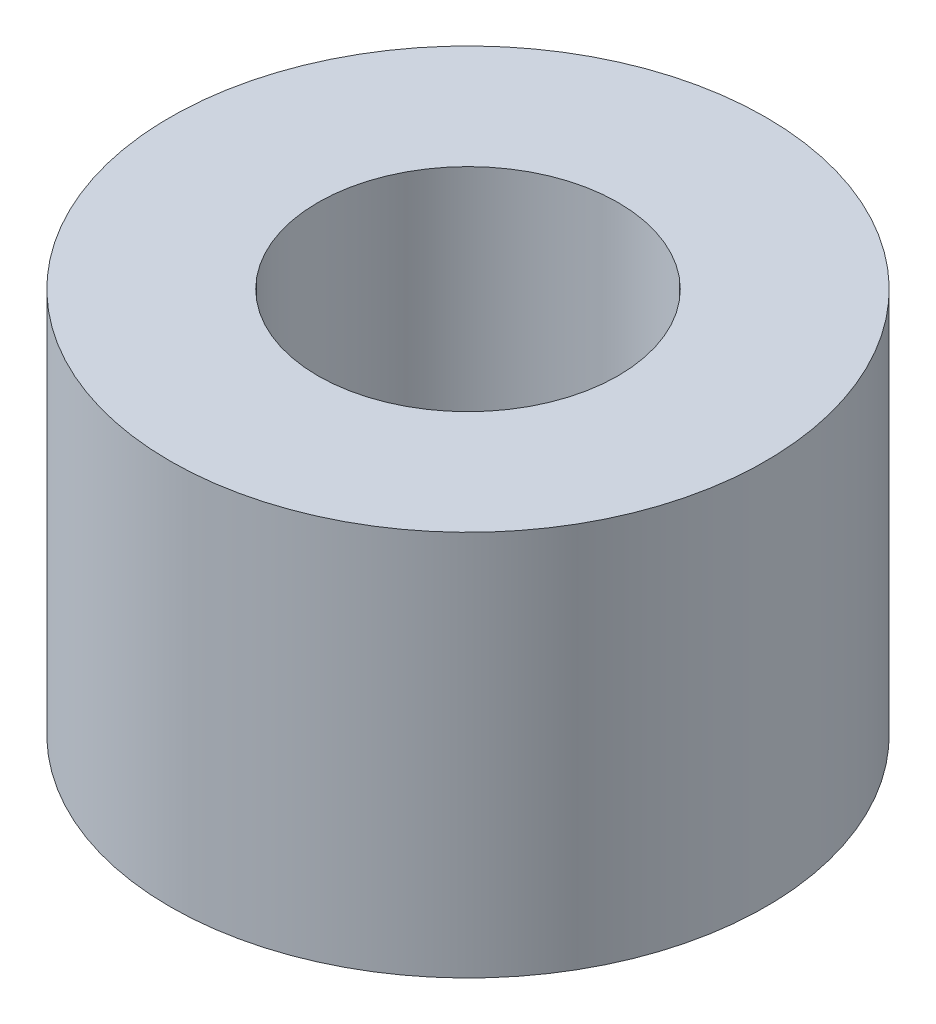
SolidWorks part; units mm, degrees
ref_plane "Front Plane" through (0, 0, 0) normal (0, 0, 1) x (1, 0, 0)
ref_plane "Top Plane" through (0, 0, 0) normal (0, 1, 0) x (1, 0, 0)
ref_plane "Right Plane" through (0, 0, 0) normal (1, 0, 0) x (0, 0, -1)
sketch "Sketch1" plane through (0, 0, 0) normal (0, 1, 0) x (1, 0, 0)
  circle A0 centre (0, 0) radius 8.001
  circle A1 centre (0, 0) radius 15.875
  dimension "D1" = 16.002
  dimension "D2" = 31.75
extrude "Boss-Extrude1" add sketch "Sketch1" along normal mid plane 20.574
